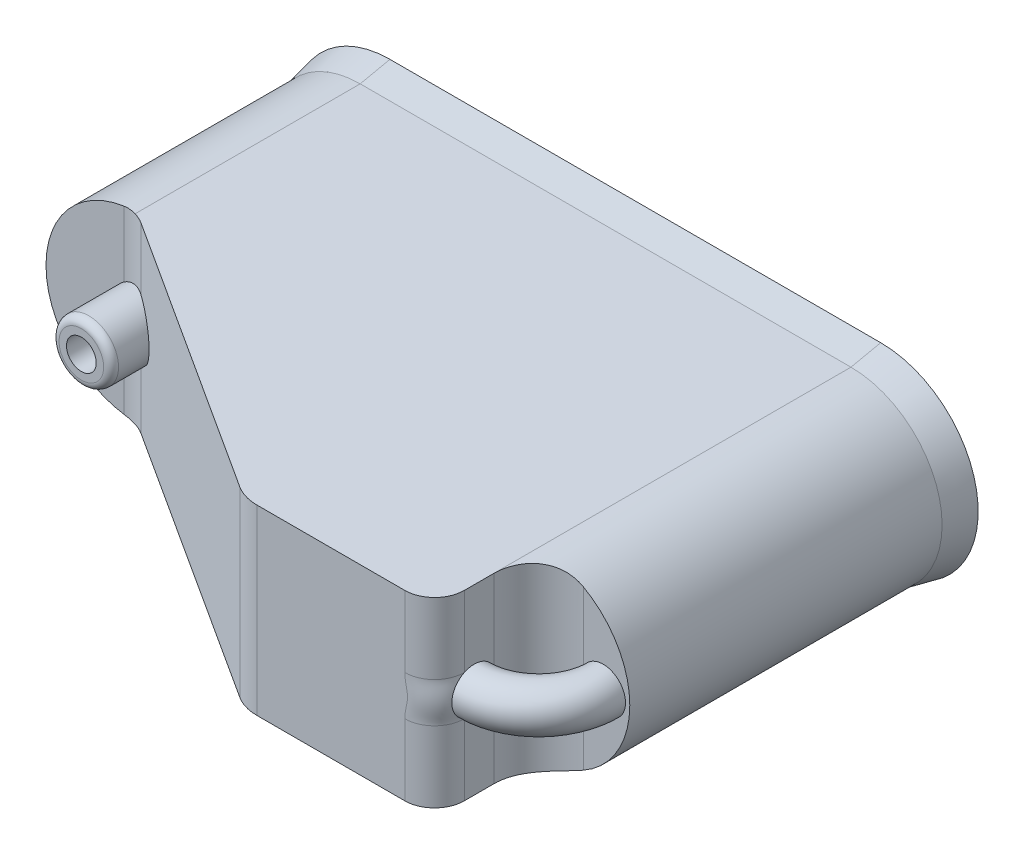
SolidWorks part; units mm, degrees
ref_plane "Front Plane" through (0, 0, 0) normal (0, 0, 1) x (1, 0, 0)
ref_plane "Top Plane" through (0, 0, 0) normal (0, 1, 0) x (1, 0, 0)
ref_plane "Right Plane" through (0, 0, 0) normal (1, 0, 0) x (0, 0, -1)
sketch "Sketch5" plane through (0, 0, 0) normal (0, 1, 0) x (1, 0, 0)
  line L0 (-165, 0) -> (165, 0) construction
  line L1 (-165, 59) -> (165, 59)
  line L2 (-165, 59) -> (-165, -59)
  line L3 (-165, -59) -> (165, -59)
  line L4 (165, 59) -> (165, -59)
  line L5 (-165, 59) -> (165, -59) construction
  line L6 (-165, -59) -> (165, 59) construction
  line L7 (-165, 65.5291) -> (165, 65.5291)
  line L8 (-165, -65.5291) -> (165, -65.5291)
  arc A0 (-165, 65.5291) -> (-165, -65.5291) centre (-165, 0) ccw
  arc A1 (165, -65.5291) -> (165, 65.5291) centre (165, 0) ccw
  point P0 (0, 0)
  point P8 (0, 0)
  dimension "D1" = 118
  dimension "D2" = 330
extrude "Boss-Extrude5" add sketch "Sketch5" along normal blind 20 draft 12 contours A0 L8 A1 L7
sketch "Sketch6" plane through (0, 20, 0) normal (0, 1, 0) x (1, 0, 0)
  line L0 (165, 61.2779) -> (165, -61.2779)
  line L1 (165, 61.2779) -> (36.681, 61.2779)
  line L2 (165, -61.2779) -> (36.681, -61.2779)
  line L3 (36.681, 61.2779) -> (36.681, -61.2779)
extrude "Boss-Extrude6" add sketch "Sketch6" along normal blind 280
sketch "Sketch7" plane through (0, 0, 61.2779) normal (0, 0, 1) x (1, 0, 0)
  line L0 (36.681, 300) -> (36.681, 20)
  line L1 (36.681, 20) -> (-165, 20)
  line L2 (-165, 20) -> (-165, 170)
  line L3 (-165, 170) -> (36.681, 300)
  dimension "D1" = 150
extrude "Boss-Extrude7" add sketch "Sketch7" against normal up to surface (122.5559 mm away) up to face at (100.8405, 160, -61.2779)
sketch "Sketch8" plane through (0, 20, 0) normal (0, 1, 0) x (1, 0, 0)
  line L0 (-165, 61.2779) -> (-165, -61.2779)
  arc A0 (-165, 61.2779) -> (-165, -61.2779) centre (-165, 0) ccw
extrude "Boss-Extrude8" add sketch "Sketch8" along normal blind 150
sketch "Sketch10" plane through (0, 0, 0) normal (0, -1, 0) x (1, 0, 0)
  line L0 (0, 0) -> (162.5, 0)
  circle A0 centre (162.5, 0) radius 10
  dimension "D2" = 20
  dimension "D1" = 162.5
extrude "Boss-Extrude9" add sketch "Sketch10" along normal blind 35 contours A0
sketch "Sketch11" plane through (0, 0, 0) normal (0, -1, 0) x (1, 0, 0)
  line L0 (0, 0) -> (-162.5, 0)
  circle A0 centre (-162.5, 0) radius 10
  dimension "D2" = 20
  dimension "D1" = 162.5
sketch "Sketch13" plane through (0, 0, 0) normal (0, -1, 0) x (1, 0, 0)
  line L0 (-181.9351, 0) -> (-143.0649, 0) construction
  line L1 (0, 0) -> (-162.5, 0) construction
  line L2 (-181.9351, 24.0728) -> (-143.0649, 24.0728)
  line L3 (-181.9351, -24.0728) -> (-143.0649, -24.0728)
  arc A0 (-181.9351, 24.0728) -> (-181.9351, -24.0728) centre (-181.9351, 0) ccw
  arc A1 (-143.0649, -24.0728) -> (-143.0649, 24.0728) centre (-143.0649, 0) ccw
  point P5 (-162.5, 0)
extrude "Boss-Extrude11" add sketch "Sketch13" along normal blind 40
sketch "Sketch14" plane through (0, 0, 0) normal (0, -1, 0) x (1, 0, 0)
  circle A0 centre (-162.5, 0) radius 20
  dimension "D1" = 40
extrude "Boss-Extrude12" add sketch "Sketch14" against normal blind 210
extrude "Cut-Extrude3" cut sketch "Sketch11" against normal up to surface and the other way up to surface contours A0 up to face at (-162.5, 210, -20) other way up to face at (-162.5, -40, 0)
sketch "Sketch15" plane through (0, 20, 0) normal (0, 1, 0) x (1, 0, 0)
  line L0 (165, 61.2779) -> (165, -61.2779)
  arc A0 (165, -61.2779) -> (165, 61.2779) centre (165, 0) ccw
extrude "Boss-Extrude13" add sketch "Sketch15" along normal blind 210
sketch "Sketch16" plane through (165, 0, 0) normal (1, 0, 0) x (0, 0, -1)
  circle A0 centre (0, 273.3956) radius 15
  dimension "D1" = 30
sketch "Sketch17" plane through (0, 0, 61.2779) normal (0, 0, 1) x (1, 0, 0)
  line L0 (165, 258.3956) -> (165, 288.3956) construction
  line L1 (226.2779, 230) -> (165, 230) construction
  arc A0 (165, 273.3956) -> (208.3956, 230) centre (165, 230) cw
sketch "Sketch18" plane through (0, 230, 0) normal (0, 1, 0) x (1, 0, 0)
sweep "Sweep1" add profiles "Sketch16" path "Sketch17"
fillet "Fillet6" radius 30 1 edges at (36.681, 300, 0)
fillet "Fillet7" radius 30 2 edges at (-165, 170, -40.5605) (-165, 170, 40.5605)
fillet "Fillet8" radius 30 1 edges at (165, 230, 0)
fillet "Fillet9" radius 20 1 edges at (165, 300, 0)
fillet "Fillet10" radius 5 1 edges at (-162.5, 210, -20)
sketch "Sketch20" plane through (0, 0, 0) normal (0, -1, 0) x (1, 0, 0)
  point P0 (162.5, 0)
move or copy body "Body-Move/Copy1" bodies to move or copy 117 copy no translate (-162.5, 0, 0)
move or copy body "Body-Move/Copy2" bodies to move or copy 118 copy no rotation origin (0, 0, 0) rotation axis (1, 0, 0) rotation angle 90
